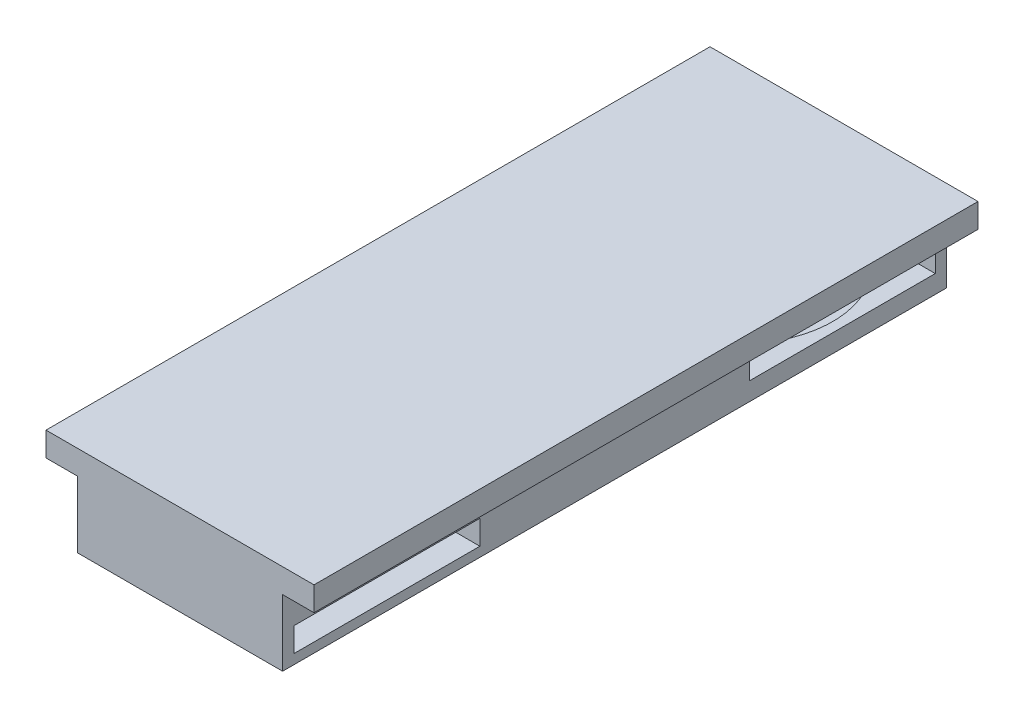
SolidWorks part; units mm, degrees
ref_plane "Front Plane" through (0, 0, 0) normal (0, 0, 1) x (1, 0, 0)
ref_plane "Top Plane" through (0, 0, 0) normal (0, 1, 0) x (1, 0, 0)
ref_plane "Right Plane" through (0, 0, 0) normal (1, 0, 0) x (0, 0, -1)
sketch "Sketch2" plane through (0, 0, 0) normal (0, 0, 1) x (1, 0, 0)
  line L0 (2.6, -2.2808) -> (19.6, -2.2808)
  line L1 (2.6, -2.2808) -> (2.6, 3.2192)
  line L2 (19.6, -2.2808) -> (19.6, 3.2192)
  line L3 (2.6, 3.2192) -> (0, 3.2192)
  line L4 (0, 3.2192) -> (0, 5.2192)
  line L5 (22.2, 5.2192) -> (22.2, 3.2192)
  line L6 (22.2, 3.2192) -> (19.6, 3.2192)
  line L7 (0, 5.2192) -> (22.2, 5.2192)
  line L8 (0, -55) -> (0, 55) construction
  dimension "D1" = 2
  dimension "D2" = 2
  dimension "D3" = 17
  dimension "D4" = 5.5
  dimension "D5" = 2.6
  dimension "D6" = 2.6
extrude "Boss-Extrude1" add sketch "Sketch2" against normal blind 55
sketch "Sketch3" plane through (0, -2.2808, 0) normal (0, -1, 0) x (1, 0, 0)
  line L0 (11.1, -46.36) -> (11.1, -54.832) construction
  line L5 (2.6, -27.5) -> (11.1, -27.5) construction
  line L6 (11.1, -8.64) -> (11.1, -46.36) construction
  line L11 (55, 0) -> (-55, 0) construction
  line L12 (2.6, -55) -> (19.6, -55) construction
  line L14 (19.6, -55) -> (19.6, 0) construction
  line L15 (2.6, -55) -> (2.6, 0) construction
  circle A2 centre (11.1, -8.64) radius 7.7
  circle A3 centre (11.1, -46.36) radius 7.7
  point P14 (11.1, -27.5)
  dimension "D1" = 15.4
  dimension "D2" = 15.4
  dimension "D3" = 8.64
  dimension "D4" = 46.36
  dimension "D5" = 8.472
  dimension "D6" = 8.64
  dimension "D7" = 8.5
  dimension "D8" = 8.5
extrude "Cut-Extrude1" cut sketch "Sketch3" against normal blind 2.8
sketch "Sketch4" plane through (0, -2.2808, 0) normal (0, -1, 0) x (1, 0, 0)
  circle A0 centre (11.1, -8.64) radius 7.7
  circle A1 centre (11.1, -46.36) radius 7.7
  circle A2 centre (11.1, -8.64) radius 5.5
  circle A3 centre (11.1, -46.36) radius 5.5
  dimension "D1" = 11
  dimension "D2" = 11
extrude "Boss-Extrude2" add sketch "Sketch4" against normal blind 0.8
sketch "Sketch5" plane through (19.6, 0, 0) normal (1, 0, 0) x (0, 0, -1)
  line L1 (0.94, 0.5192) -> (16.34, 0.5192)
  line L2 (0.94, 0.5192) -> (0.94, -1.4808)
  line L3 (0.94, -1.4808) -> (16.34, -1.4808)
  line L4 (16.34, 0.5192) -> (16.34, -1.4808)
  line L5 (38.66, 1.2192) -> (54.06, 1.2192)
  line L6 (38.66, 1.2192) -> (38.66, -0.7808)
  line L7 (38.66, -0.7808) -> (54.06, -0.7808)
  line L8 (54.06, 1.2192) -> (54.06, -0.7808)
  line L10 (55, -2.2808) -> (0, -2.2808) construction
  line L11 (0.94, 0.5192) -> (0.94, -1.4808) construction
  line L12 (54.06, -1.4808) -> (54.06, 0.5192) construction
  dimension "D1" = 0
  dimension "D2" = 0
  dimension "D3" = 15.4
  dimension "D4" = 15.4
  dimension "D5" = 0.8
  dimension "D6" = 1.5
  dimension "D7" = 2
  dimension "D8" = 2
extrude "Cut-Extrude2" cut sketch "Sketch5" against normal blind 8.5
